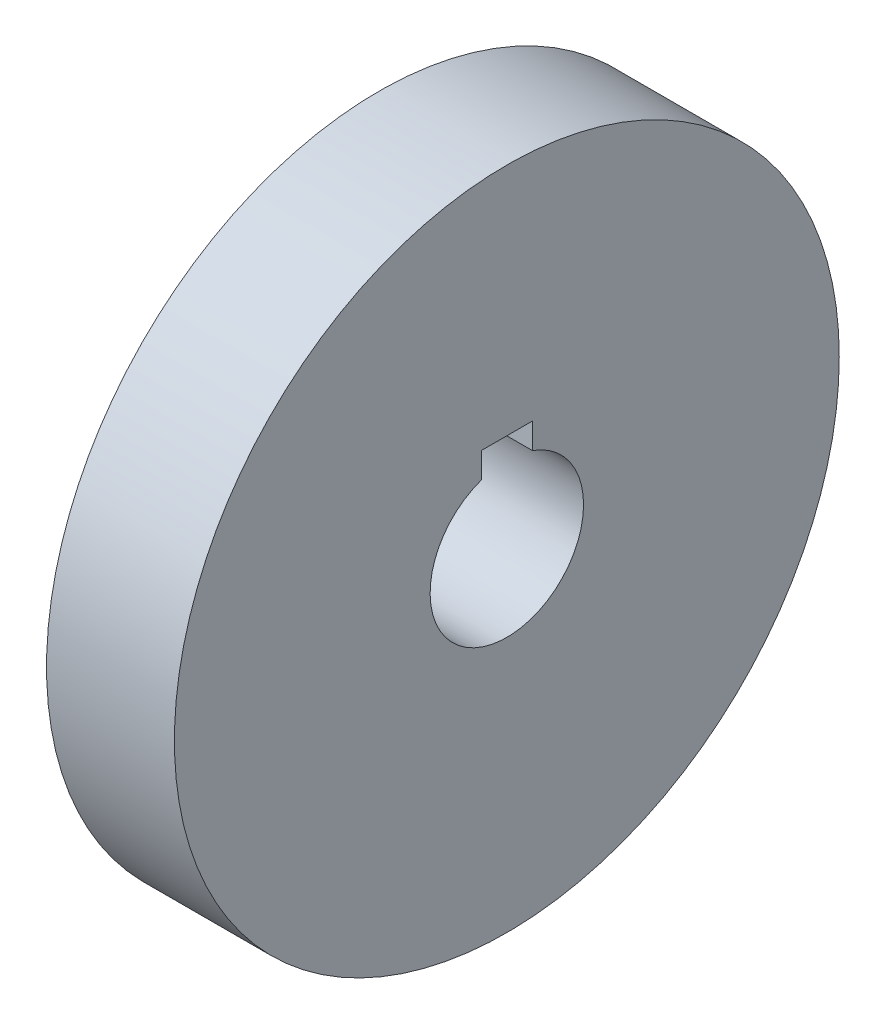
SolidWorks part; units mm, degrees
ref_plane "Front Plane" through (0, 0, 0) normal (0, 0, 1) x (1, 0, 0)
ref_plane "Top Plane" through (0, 0, 0) normal (0, 1, 0) x (1, 0, 0)
ref_plane "Right Plane" through (0, 0, 0) normal (1, 0, 0) x (0, 0, -1)
sketch "Sketch1" plane through (0, 0, 0) normal (1, 0, 0) x (0, 0, -1)
  line L0 (0, 0) -> (0, 6) construction
  line L1 (2, 7.6569) -> (-2, 7.6569)
  line L2 (-2, 7.6569) -> (-2, 5.6569)
  line L3 (2, 7.6569) -> (2, 5.6569)
  circle A0 centre (0, 0) radius 26
  arc A1 (-2, 5.6569) -> (2, 5.6569) centre (0, 0) ccw
  point P10 (0, 7.6569)
  dimension "D1" = 52
  dimension "D2" = 12
  dimension "D3" = 4
  dimension "D4" = 2
extrude "Boss-Extrude1" add sketch "Sketch1" along normal blind 10
